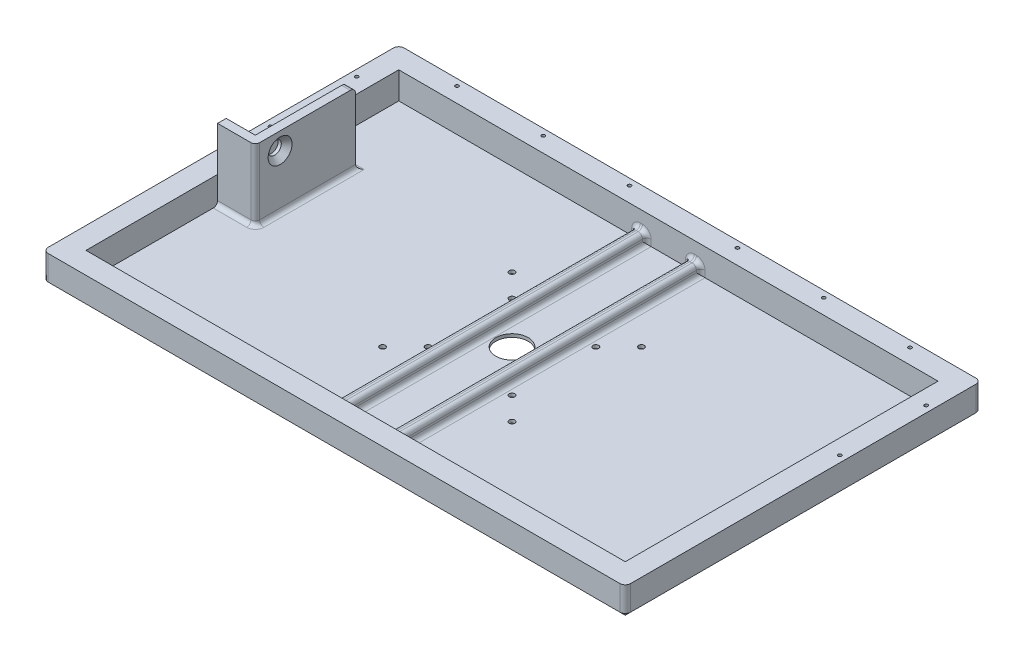
SolidWorks part; units mm, degrees
ref_plane "Front Plane" through (0, 0, 0) normal (0, 0, 1) x (1, 0, 0)
ref_plane "Top Plane" through (0, 0, 0) normal (0, 1, 0) x (1, 0, 0)
ref_plane "Right Plane" through (0, 0, 0) normal (1, 0, 0) x (0, 0, -1)
sketch "Sketch1" plane through (0, 0, 0) normal (0, 1, 0) x (1, 0, 0)
  line L1 (-270, -165) -> (270, -165)
  line L2 (-270, -165) -> (-270, 165)
  line L3 (-270, 165) -> (270, 165)
  line L4 (270, -165) -> (270, 165)
  line L5 (-270, -165) -> (270, 165) construction
  line L6 (-270, 165) -> (270, -165) construction
  point P0 (0, 0)
  dimension "D1" = 540
  dimension "D2" = 330
extrude "Boss-Extrude1" add sketch "Sketch1" along normal blind 3
sketch "Sketch2" plane through (0, 3, 0) normal (0, 1, 0) x (1, 0, 0)
  line L0 (250, 145) -> (-250, 145)
  line L1 (270, -165) -> (-270, -165)
  line L2 (270, -165) -> (270, 165)
  line L3 (270, 165) -> (-270, 165)
  line L4 (-270, -165) -> (-270, 165)
  line L5 (270, -165) -> (-270, 165) construction
  line L6 (270, 165) -> (-270, -165) construction
  line L7 (-250, -145) -> (-250, 145)
  line L8 (250, -145) -> (-250, -145)
  line L9 (250, -145) -> (250, 145)
  point P0 (0, 0)
  dimension "D1" = 20
  dimension "D2" = 540
extrude "Boss-Extrude2" add sketch "Sketch2" along normal blind 25 contours L0 L7 L8 L9 | L2 L1 L4 L3
fillet "Fillet1" radius 5 4 edges at (-270, 14, -165) (-270, 14, 165) (270, 14, 165) (270, 14, -165)
sketch "Sketch4" plane through (0, 28, 0) normal (0, 1, 0) x (1, 0, 0)
  line L0 (-270, 0) -> (-264, 0) construction
  line L1 (-270, -160) -> (-270, 160) construction
  line L2 (-264, 0) -> (-264, 40) construction
  line L3 (-264, 40) -> (-264, 120) construction
  line L4 (0, 0) -> (0, 145) construction
  line L5 (250, 145) -> (-250, 145) construction
  line L6 (0, 165) -> (0, 159) construction
  line L7 (265, 165) -> (-265, 165) construction
  line L8 (0, 159) -> (-50, 159) construction
  line L9 (-50, 159) -> (-130, 159) construction
  line L10 (-130, 159) -> (-210, 159) construction
  line L11 (130, 159) -> (210, 159) construction
  line L12 (50, 159) -> (130, 159) construction
  line L13 (264, 40) -> (264, 120) construction
  circle A0 centre (-264, 120) radius 1.6
  circle A1 centre (-264, 40) radius 1.6
  circle A2 centre (-210, 159) radius 1.6
  circle A3 centre (-130, 159) radius 1.6
  circle A4 centre (-50, 159) radius 1.6
  circle A5 centre (50, 159) radius 1.6
  circle A6 centre (130, 159) radius 1.6
  circle A7 centre (210, 159) radius 1.6
  circle A8 centre (264, 40) radius 1.6
  circle A9 centre (264, 120) radius 1.6
  dimension "D1" = 50
  dimension "D2" = 80
  dimension "D3" = 80
  dimension "D4" = 6
  dimension "D5" = 6
  dimension "D6" = 40
  dimension "D7" = 80
extrude "Cut-Extrude1" cut sketch "Sketch4" against normal up to surface (28 mm away) up to face at (0, 0, 0)
sketch "Sketch5" plane through (0, 3, 0) normal (0, 1, 0) x (1, 0, 0)
  circle A0 centre (0, 0) radius 15
  dimension "D1" = 30
extrude "Cut-Extrude2" cut sketch "Sketch5" against normal up to surface (3 mm away) up to face at (-264, 0, -41.6)
sketch "Sketch6" plane through (0, 3, 0) normal (0, 1, 0) x (1, 0, 0)
  line L0 (0, 145) -> (25, 145) construction
  line L1 (250, 145) -> (-250, 145) construction
  line L2 (25, 145) -> (25, -145) construction
  line L3 (250, -145) -> (-250, -145) construction
  line L4 (0, 145) -> (-25, 145) construction
  line L5 (250, 145) -> (-250, 145) construction
  line L6 (-25, 145) -> (-25, -145) construction
  line L7 (250, -145) -> (-250, -145) construction
  line L9 (20, -145) -> (30, -145)
  line L10 (20, -145) -> (20, 145)
  line L11 (20, 145) -> (30, 145)
  line L12 (30, -145) -> (30, 145)
  line L13 (20, -145) -> (30, 145) construction
  line L14 (20, 145) -> (30, -145) construction
  line L15 (-30, -145) -> (-20, -145)
  line L16 (-30, -145) -> (-30, 145)
  line L17 (-30, 145) -> (-20, 145)
  line L18 (-20, -145) -> (-20, 145)
  line L19 (-30, -145) -> (-20, 145) construction
  line L20 (-30, 145) -> (-20, -145) construction
  point P13 (25, 0)
  point P19 (-25, 0)
  dimension "D1" = 25
  dimension "D2" = 25
  dimension "D3" = 10
  dimension "D4" = 10
extrude "Boss-Extrude3" add sketch "Sketch6" along normal blind 10
fillet "Fillet3" radius 4 20 edges at (20, 8, 145) (30, 8, 145) (20, 8, -145) (30, 8, -145) (-30, 8, 145) (-20, 8, 145) (-20, 8, -145) (-30, 8, -145) (-20, 3, 0) (20, 3, 0) (25, 13, 145) (20, 13, 0) (25, 13, -145) (30, 13, 0) (-25, 13, 145) (-25, 13, -145) (-30, 3, 0) (-20, 13, 0) (-30, 13, 0) (30, 3, 0)
chamfer "Chamfer1" distance 5 angle 45 8 edges at (270, 0, 0) (0, 0, -165) (0, 0, 165) (268.5355, 0, -163.5355) (268.5355, 0, 163.5355) (-268.5355, 0, -163.5355) (-268.5355, 0, 163.5355) (-270, 0, 0)
sketch "Sketch7" plane through (0, 0, 0) normal (0, -1, 0) x (1, 0, 0)
  line L1 (-60, -60) -> (60, -60) construction
  line L2 (-60, -60) -> (-60, 60) construction
  line L3 (-60, 60) -> (60, 60) construction
  line L4 (60, -60) -> (60, 60) construction
  line L5 (-60, -60) -> (60, 60) construction
  line L6 (-60, 60) -> (60, -60) construction
  circle A0 centre (-60, 60) radius 2.6
  circle A1 centre (60, 60) radius 2.6
  circle A2 centre (60, -60) radius 2.6
  circle A3 centre (-60, -60) radius 2.6
  point P0 (0, 0)
  dimension "D1" = 120
  dimension "D2" = 120
extrude "Cut-Extrude3" cut sketch "Sketch7" against normal up to surface (3 mm away) up to face at (-142, 3, 0)
sketch "Sketch9" plane through (0, 0, 0) normal (0, -1, 0) x (1, 0, 0)
  line L1 (-38.8909, -38.8909) -> (38.8909, -38.8909) construction
  line L2 (-38.8909, -38.8909) -> (-38.8909, 38.8909) construction
  line L3 (-38.8909, 38.8909) -> (38.8909, 38.8909) construction
  line L4 (38.8909, -38.8909) -> (38.8909, 38.8909) construction
  line L5 (-38.8909, -38.8909) -> (38.8909, 38.8909) construction
  line L6 (-38.8909, 38.8909) -> (38.8909, -38.8909) construction
  circle A0 centre (-38.8909, 38.8909) radius 2.6
  circle A1 centre (38.8909, 38.8909) radius 2.6
  circle A2 centre (38.8909, -38.8909) radius 2.6
  circle A3 centre (-38.8909, -38.8909) radius 2.6
  point P0 (0, 0)
  dimension "D1" = 110
  dimension "D2" = 110
extrude "Cut-Extrude4" cut sketch "Sketch9" against normal blind 47
sketch "Sketch11" plane through (0, 3, 0) normal (0, 1, 0) x (1, 0, 0)
  line L0 (-250, 0) -> (-34, 0) construction
  line L1 (-250, -145) -> (-250, 145) construction
  line L2 (-34, -145) -> (-34, 145) construction
  line L3 (-250, 0) -> (-219, 0) construction
  line L5 (-223, 70) -> (-215, 70)
  line L6 (-223, 70) -> (-223, -70)
  line L7 (-223, -70) -> (-215, -70)
  line L8 (-215, 70) -> (-215, -70)
  line L9 (-223, 70) -> (-215, -70) construction
  line L10 (-223, -70) -> (-215, 70) construction
  point P11 (0, 0)
  point P12 (0, 0)
  dimension "D1" = 31
  dimension "D2" = 140
  dimension "D3" = 8
  dimension "D4" = 31
extrude "Boss-Extrude4" add sketch "Sketch11" along normal blind 66
sketch "Sketch12" plane through (-223, 0, 0) normal (-1, 0, 0) x (0, 0, 1)
  line L0 (0, 0) -> (0, 28) construction
  line L1 (160, 28) -> (-160, 28) construction
  line L2 (0, 28) -> (0, 53) construction
  circle A0 centre (0, 53) radius 6.1
  dimension "D2" = 12.2
  dimension "D1" = 25
extrude "Cut-Extrude5" cut sketch "Sketch12" against normal up to surface (8 mm away) up to face at (-215, 36, 0)
sketch "Sketch13" plane through (-223, 0, 0) normal (-1, 0, 0) x (0, 0, 1)
  line L0 (0, 0) -> (0, 69) construction
  line L1 (-70, 69) -> (70, 69) construction
  line L2 (0, 69) -> (15, 69) construction
  line L3 (160, 0) -> (-38.751, 0) construction
  line L4 (15, 69) -> (23, 69)
  line L5 (15, 69) -> (15, 0)
  line L6 (15, 0) -> (23, 0)
  line L7 (23, 69) -> (23, 0)
  line L8 (0, 0) -> (0, 53) construction
  line L9 (0, 53) -> (-50, 53) construction
  line L10 (-50, 53) -> (-50, 40.75) construction
  line L11 (-41.249, 0) -> (-118.751, 0) construction
  line L12 (-50, 40.75) -> (-70, 40.75)
  line L13 (-50, 40.75) -> (-50, 0)
  line L14 (-50, 0) -> (-70, 0)
  line L15 (-70, 40.75) -> (-70, 0)
  dimension "D1" = 15
  dimension "D2" = 8
  dimension "D3" = 12.25
  dimension "D4" = 50
  dimension "D5" = 20
extrude "Boss-Extrude5" add sketch "Sketch13" along normal up to surface (27 mm away) up to face at (-250, 15.5, 0)
sketch "Sketch15" plane through (0, 69, 0) normal (0, 1, 0) x (1, 0, 0)
  line L0 (-250, -23) -> (-223, -23) construction
  line L1 (-215, -70) -> (-223, -70)
  line L2 (-215, -70) -> (-215, -23)
  line L3 (-215, -23) -> (-223, -23)
  line L4 (-223, -70) -> (-223, -23)
  line L5 (-223, -23) -> (-223, -70) construction
extrude "Cut-Extrude6" cut sketch "Sketch15" against normal up to surface (66 mm away) up to face at (-60, 3, 57.4)
fillet "Fillet4" radius 4 4 edges at (-215, 3, -23.5) (-232.5, 3, -70) (-232.5, 3, 23) (-215, 36, 23)
fillet "Fillet5" radius 10 1 edges at (-223, 40.75, -60)
fillet "Fillet6" radius 5 1 edges at (-250, 40.75, -60)
fillet "Fillet7" radius 5 1 edges at (-219, 69, -70)
chamfer "Chamfer2" distance 5 angle 45 1 edges at (-215, 53, 6.1)
sketch "Sketch16" plane through (0, 28, 0) normal (0, 1, 0) x (1, 0, 0)
  line L0 (-250, 145) -> (-250, 70) construction
  line L1 (-250, -145) -> (250, -145)
  line L2 (-250, -145) -> (-250, -23)
  line L3 (-250, 145) -> (250, 145)
  line L4 (250, -145) -> (250, 145)
  line L5 (-250, -145) -> (250, 145) construction
  line L6 (-250, 145) -> (250, -145) construction
  line L7 (-250, 70) -> (-215, 70)
  line L8 (-215, 70) -> (-215, -23)
  line L9 (-215, -23) -> (-250, -23)
  line L10 (-250, 70) -> (-250, 145)
  point P0 (0, 0)
  point P12 (-232.5, -23)
  dimension "D1" = 290
  dimension "D2" = 500
  dimension "D3" = 93
  dimension "D4" = 35
  dimension "D5" = 168
  dimension "D6" = 75
